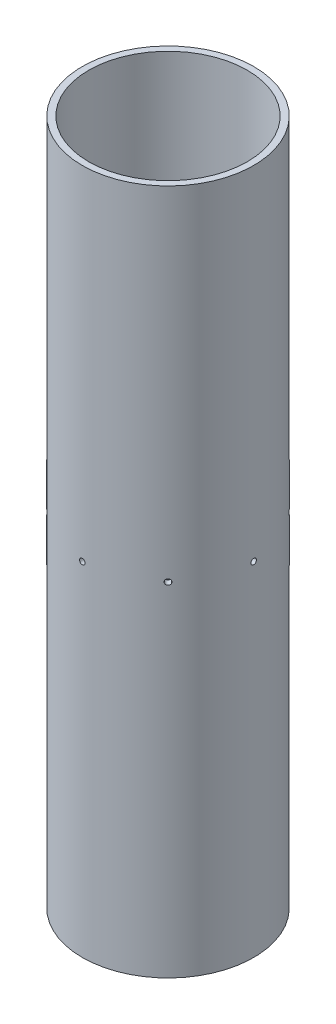
SolidWorks part; units mm, degrees
material "E-Glass Fiber"
ref_plane "Front Plane" through (0, 0, 0) normal (0, 0, 1) x (1, 0, 0)
ref_plane "Top Plane" through (0, 0, 0) normal (0, 1, 0) x (1, 0, 0)
ref_plane "Right Plane" through (0, 0, 0) normal (1, 0, 0) x (0, 0, -1)
sketch "Sketch1" plane through (0, 0, 0) normal (0, 1, 0) x (1, 0, 0)
  circle A0 centre (0, 0) radius 50.8
  dimension "D1" = 101.6
extrude "Coupler Extrusion" add sketch "Sketch1" along normal blind 406.4 thin thin type one direction reverse wall 3.81
ref_plane "Plane1" through (0, 0, 50.8) normal (0, 0, 1) x (1, 0, 0)
sketch "Sketch2" plane through (0, 0, 50.8) normal (0, 0, 1) x (1, 0, 0)
  line L0 (0, 406.4) -> (0, 0) construction
  line L1 (46.99, 406.4) -> (-46.99, 406.4) construction
  circle A0 centre (0, 203.2) radius 1.6383
  dimension "D1" = 3.2766
  dimension "D2" = 203.2
extrude "Bulkhead Hole" cut sketch "Sketch2" against normal up to next
pattern_circular "CirPattern1" count 8 over 360 about axis through (0, 406.4, 0) along (0, -1, 0) of "Bulkhead Hole"
